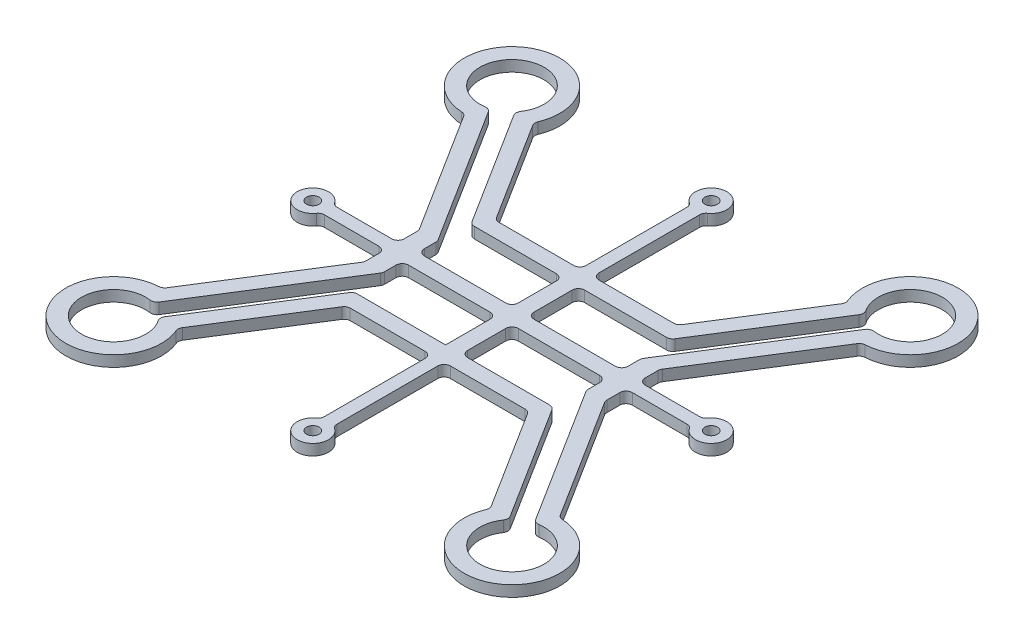
SolidWorks part; units mm, degrees
material "Hexcel AS4C (3000 Filaments)"
ref_plane "Front Plane" through (0, 0, 0) normal (0, 0, 1) x (1, 0, 0)
ref_plane "Top Plane" through (0, 0, 0) normal (0, 1, 0) x (1, 0, 0)
ref_plane "Right Plane" through (0, 0, 0) normal (1, 0, 0) x (0, 0, -1)
sketch "Sketch1" plane through (0, 0, 0) normal (0, 1, 0) x (1, 0, 0)
  line L0 (0, 28.7416) -> (0, -31.95) construction
  line L1 (-19.25, 11.875) -> (19.25, 11.875)
  line L2 (-19.25, 11.875) -> (-19.25, -11.875)
  line L3 (-19.25, -11.875) -> (19.25, -11.875)
  line L4 (19.25, 11.875) -> (19.25, -11.875)
  line L5 (-19.25, 11.875) -> (19.25, -11.875) construction
  line L6 (-19.25, -11.875) -> (19.25, 11.875) construction
  line L7 (-23.7954, 0) -> (45.7192, 0) construction
  line L8 (-31.8198, 4.3198) -> (-31.8198, -4.3198) construction
  line L9 (-31.8198, -31.8198) -> (-31.8198, 31.8198) construction
  line L10 (-31.8198, 31.8198) -> (-19.25, 11.875) construction
  line L11 (19.25, 9.825) -> (-13.5, 9.825)
  line L12 (19.25, 9.825) -> (19.25, -9.825)
  line L13 (19.25, -9.825) -> (-13.5, -9.825)
  line L14 (-13.5, 9.825) -> (-13.5, -9.825)
  line L15 (19.25, 9.825) -> (-13.5, -9.825) construction
  line L16 (19.25, -9.825) -> (-13.5, 9.825) construction
  line L17 (-31.727, 24.1704) -> (-19.25, 4.3728)
  line L18 (-24.959, 28.4358) -> (-14.5219, 11.875)
  line L19 (-35.2038, 29.6871) -> (-22.634, 9.7423) construction
  line L20 (-28.4358, 33.9525) -> (-15.866, 14.0077) construction
  line L21 (24.959, 28.4358) -> (14.5219, 11.875)
  line L22 (31.727, 24.1704) -> (19.25, 4.3728)
  line L23 (24.959, -28.4358) -> (14.5219, -11.875)
  line L24 (31.727, -24.1704) -> (19.25, -4.3728)
  line L25 (-24.959, -28.4358) -> (-14.5219, -11.875)
  line L26 (-31.727, -24.1704) -> (-19.25, -4.3728)
  line L27 (-31.8198, 31.8198) -> (31.8198, 31.8198) construction
  circle A0 centre (-31.8198, 31.8198) radius 27.5
  circle A1 centre (31.8198, 31.8198) radius 27.5
  circle A2 centre (-31.8198, -31.8198) radius 27.5
  circle A3 centre (31.8198, -31.8198) radius 27.5
  circle A4 centre (-31.8198, 31.8198) radius 7.65
  circle A5 centre (-31.8198, 31.8198) radius 5.125
  circle A6 centre (31.8198, 31.8198) radius 5.125
  circle A7 centre (31.8198, 31.8198) radius 7.65
  circle A8 centre (31.8198, -31.8198) radius 5.125
  circle A9 centre (31.8198, -31.8198) radius 7.65
  circle A10 centre (-31.8198, -31.8198) radius 5.125
  circle A11 centre (-31.8198, -31.8198) radius 7.65
  point P0 (0, 0)
  point P18 (2.875, 0)
  dimension "D3" = 55
  dimension "D8" = 15.3
  dimension "D9" = 10.25
  dimension "D1" = 23.75
  dimension "D2" = 38.5
  dimension "D4" = 19.65
  dimension "D5" = 32.75
  dimension "D10" = 8
  dimension "D6" = 90
extrude "Boss-Extrude1" add sketch "Sketch1" along normal blind 1.75 contours A4 A5 | A4 L17 L2 L1 L18 | A11 A10 | L26 A11 L25 L3 L2 | A9 A8 | A9 L24 L4 L3 L23 | A7 A6 | L22 A7 L21 L1 L4 | L26 A2 L2 | A0 L17 L2 | A3 L24 L4 | L22 A1 L12 | L1 L4 L3 L2 region at (-23.128, 0, -17.8619) region at (-19.7311, 0, -6.1292) region at (-27.8564, 0, -25.5309) region at (-19.7311, 0, 6.1292) region at (23.128, 0, -17.8619) region at (-23.128, 0, 17.8619) region at (30.1315, 0, -39.0592) region at (19.7311, 0, -6.1292) region at (-27.8564, 0, 25.5309) region at (19.7311, 0, 6.1292) region at (23.128, 0, 17.8619) region at (27.8564, 0, 25.5309)
sketch "Sketch2" plane through (0, 1.75, 0) normal (0, 1, 0) x (1, 0, 0)
  line L0 (-19.25, 0) -> (19.25, 0) construction
  line L1 (-19.25, 4.3728) -> (-19.25, -4.3728) construction
  line L2 (19.25, 4.3728) -> (19.25, -4.3728) construction
  line L3 (0, 11.875) -> (0, -11.875) construction
  line L4 (-14.5219, 11.875) -> (14.5219, 11.875) construction
  line L5 (-14.5219, -11.875) -> (14.5219, -11.875) construction
  line L6 (-29.0873, 27.484) -> (-11.766, 0) construction
  line L7 (-31.727, 24.1704) -> (-19.25, 4.3728) construction
  line L8 (-24.959, 28.4358) -> (-14.5219, 11.875) construction
  line L9 (-30.4507, 26.881) -> (-16.2654, 4.3728)
  line L10 (-31.8198, 36.9448) -> (-31.8198, 39.4698) construction
  line L11 (-23.3581, 15.6269) -> (-25.4942, 14.2807) construction
  line L12 (-19.25, 4.3728) -> (19.25, 4.3728) construction
  line L13 (-27.955, 28.4539) -> (-12.7784, 4.3728)
  line L14 (-15.9152, 9.35) -> (15.9152, 9.35)
  line L15 (0, 9.35) -> (0, 11.875) construction
  line L16 (-16.2654, 4.3728) -> (-16.2654, -4.3728)
  line L17 (-12.7784, 4.3728) -> (-12.7784, -4.3728)
  line L18 (12.7784, 4.3728) -> (12.7784, -4.3728)
  line L19 (16.2654, 4.3728) -> (16.2654, -4.3728)
  line L20 (27.955, 28.4539) -> (12.7784, 4.3728)
  line L21 (30.4507, 26.881) -> (16.2654, 4.3728)
  line L22 (27.955, -28.4539) -> (12.7784, -4.3728)
  line L23 (30.4507, -26.881) -> (16.2654, -4.3728)
  line L24 (-15.9152, -9.35) -> (15.9152, -9.35)
  line L25 (-30.4507, -26.881) -> (-16.2654, -4.3728)
  line L26 (-27.955, -28.4539) -> (-12.7784, -4.3728)
  line L27 (-1.2625, 0) -> (1.2625, 0) construction
  line L28 (1.2625, -9.35) -> (-1.2625, -9.35)
  line L29 (1.2625, -9.35) -> (1.2625, 9.35)
  line L30 (1.2625, 9.35) -> (-1.2625, 9.35)
  line L31 (-1.2625, -9.35) -> (-1.2625, 9.35)
  line L32 (1.2625, -9.35) -> (-1.2625, 9.35) construction
  line L33 (1.2625, 9.35) -> (-1.2625, -9.35) construction
  line L35 (-16.2654, -1.2625) -> (16.2654, -1.2625)
  line L36 (-16.2654, -1.2625) -> (-16.2654, 1.2625)
  line L37 (-16.2654, 1.2625) -> (16.2654, 1.2625)
  line L38 (16.2654, -1.2625) -> (16.2654, 1.2625)
  line L39 (-16.2654, -1.2625) -> (16.2654, 1.2625) construction
  line L40 (-16.2654, 1.2625) -> (16.2654, -1.2625) construction
  circle A0 centre (-31.8198, 31.8198) radius 5.125 construction
  circle A1 centre (-31.8198, 31.8198) radius 5.125
  circle A2 centre (31.8198, 31.8198) radius 5.125
  arc A3 (-24.959, 28.4358) -> (-31.727, 24.1704) centre (-31.8198, 31.8198) ccw construction
  circle A4 centre (-31.8198, -31.8198) radius 5.125
  circle A5 centre (31.8198, -31.8198) radius 5.125
  point P39 (0, 0)
  point P41 (0, 0)
  point P42 (-16.2654, 0)
  point P45 (12.7784, 0)
  point P47 (0, 9.35)
  point P60 (16.2654, 0)
  point P66 (-12.7784, 0)
extrude "Cut-Extrude2" cut sketch "Sketch2" against normal up to next contours L16 L37 L17 L13 L33 L9 | L17 L37 L31 L14 L13 | L29 L37 L18 L20 L14 | L18 L37 L19 L21 L36 L20 | L35 L18 L22 L23 L19 | L35 L29 L24 L22 L18 | L35 L17 L26 L24 L31 | L35 L16 L25 L32 L26 L17 region at (-20.9447, 1.75, -14.4076) region at (-7.5466, 1.75, -5.4907) region at (-20.9447, 1.75, 14.4076) region at (-7.5466, 1.75, 5.4907) region at (7.5466, 1.75, -5.4907) region at (20.9447, 1.75, -14.4076) region at (7.5466, 1.75, 5.4907) region at (20.9447, 1.75, 14.4076)
sketch "Sketch3" plane through (0, 1.75, 0) normal (0, 1, 0) x (1, 0, 0)
  line L0 (0, 29.3198) -> (0, 11.875) construction
  line L1 (-14.5219, 11.875) -> (14.5219, 11.875) construction
  line L2 (-1.025, 29.5396) -> (-1.025, 11.875)
  line L3 (1.025, 29.5396) -> (1.025, 11.875)
  line L4 (-52.9945, 0) -> (60.5071, 0) construction
  line L5 (-1.025, 11.875) -> (1.025, 11.875)
  line L6 (-1.025, -29.5396) -> (-1.025, -11.875)
  line L7 (1.025, -29.5396) -> (1.025, -11.875)
  line L8 (-1.025, -11.875) -> (1.025, -11.875)
  line L9 (-29.5396, -1.025) -> (-19.25, -1.025)
  line L10 (-19.25, 4.3728) -> (-19.25, -4.3728) construction
  line L11 (-29.5396, 1.025) -> (-19.25, 1.025)
  line L12 (0, 11.875) -> (0, 9.825) construction
  line L13 (16.375, 9.825) -> (-16.375, 9.825) construction
  line L14 (-19.25, 1.025) -> (-19.25, -1.025)
  line L15 (0, -56.1075) -> (0, 58.6307) construction
  line L16 (19.25, 1.025) -> (19.25, -1.025)
  line L17 (29.5396, 1.025) -> (19.25, 1.025)
  line L18 (29.5396, -1.025) -> (19.25, -1.025)
  circle A0 centre (0, 31.8198) radius 1
  circle A1 centre (0, 31.8198) radius 1 construction
  circle A2 centre (0, 31.8198) radius 2.5
  circle A3 centre (31.8198, 0) radius 2.5
  circle A4 centre (31.8198, 0) radius 1
  circle A5 centre (0, -31.8198) radius 1
  circle A6 centre (0, -31.8198) radius 2.5
  circle A7 centre (-31.8198, 0) radius 1 construction
  circle A8 centre (-31.8198, 0) radius 1
  circle A9 centre (-31.8198, 0) radius 2.5
  line M35 (-19.25, 4.3728) -> (-19.25, -4.3728)
  line M39 (-14.5219, -11.875) -> (14.5219, -11.875)
  line M43 (19.25, -4.3728) -> (19.25, 4.3728)
  line M47 (14.5219, 11.875) -> (-14.5219, 11.875)
  dimension "D1" = 5
extrude "Boss-Extrude2" add sketch "Sketch3" against normal up to surface (1.75 mm away) contours A2 A0 | A2 L2 L3 M47 | A6 A5 | L6 A6 L7 M39 | A9 A8 | A9 L9 L11 M35 | L18 A3 L17 M43 | A3 A4 region at (0, 1.75, -20.6335) region at (-1.3194, 1.75, -33.8595) region at (0, 1.75, 20.6335) region at (0, 1.75, 29.3905) region at (-24.3211, 1.75, 0) region at (-34.2491, 1.75, 0) region at (24.3211, 1.75, 0) region at (32.3291, 1.75, -2.3753) up to face at (0, 0, 0)
fillet "Fillet1" radius 1 59 edges at (-30.4507, 0.875, 26.881) (-29.5396, 0.875, -1.025) (-31.727, 0.875, -24.1704) (-1.025, 0.875, -29.5396) (-1.2625, 0.875, -1.2625) (1.2625, 0.875, -1.2625) (-16.2654, 0.875, -1.2625) (-19.25, 0.875, 1.025) (-1.2625, 0.875, 1.2625) (-1.2625, 0.875, -9.35) (-31.727, 0.875, 24.1704) (-19.25, 0.875, 4.3728) (-19.25, 0.875, -1.025) (-19.25, 0.875, -4.3728) (24.959, 0.875, -28.4358) (-27.955, 0.875, -28.4539) (-27.955, 0.875, 28.4539) (-1.025, 0.875, -11.875) (-14.5219, 0.875, -11.875) (-15.9152, 0.875, 9.35) (1.025, 0.875, -11.875) (1.025, 0.875, -29.5396) (-30.4507, 0.875, -26.881) (-24.959, 0.875, -28.4358) (-29.5396, 0.875, 1.025) (-15.9152, 0.875, -9.35) (-16.2654, 0.875, -4.3728) (-16.2654, 0.875, 4.3728) (-16.2654, 0.875, 1.2625) (1.2625, 0.875, -9.35) (1.2625, 0.875, 1.2625) (1.2625, 0.875, 9.35) (16.2654, 0.875, -1.2625) (16.2654, 0.875, -4.3728) (15.9152, 0.875, -9.35) (14.5219, 0.875, -11.875) (30.4507, 0.875, -26.881) (27.955, 0.875, -28.4539) (31.727, 0.875, -24.1704) (19.25, 0.875, -4.3728) (19.25, 0.875, -1.025) (29.5396, 0.875, -1.025) (29.5396, 0.875, 1.025) (16.2654, 0.875, 1.2625) (16.2654, 0.875, 4.3728) (15.9152, 0.875, 9.35) (19.25, 0.875, 1.025) (19.25, 0.875, 4.3728) (31.727, 0.875, 24.1704) (30.4507, 0.875, 26.881) (27.955, 0.875, 28.4539) (24.959, 0.875, 28.4358) (14.5219, 0.875, 11.875) (1.025, 0.875, 11.875) (1.025, 0.875, 29.5396) (-1.025, 0.875, 29.5396) (-1.025, 0.875, 11.875) (-14.5219, 0.875, 11.875) (-24.959, 0.875, 28.4358)
equation "\"PropDiameter\"=55"
equation "\"D3@Sketch1\"=\"PropDiameter\""
